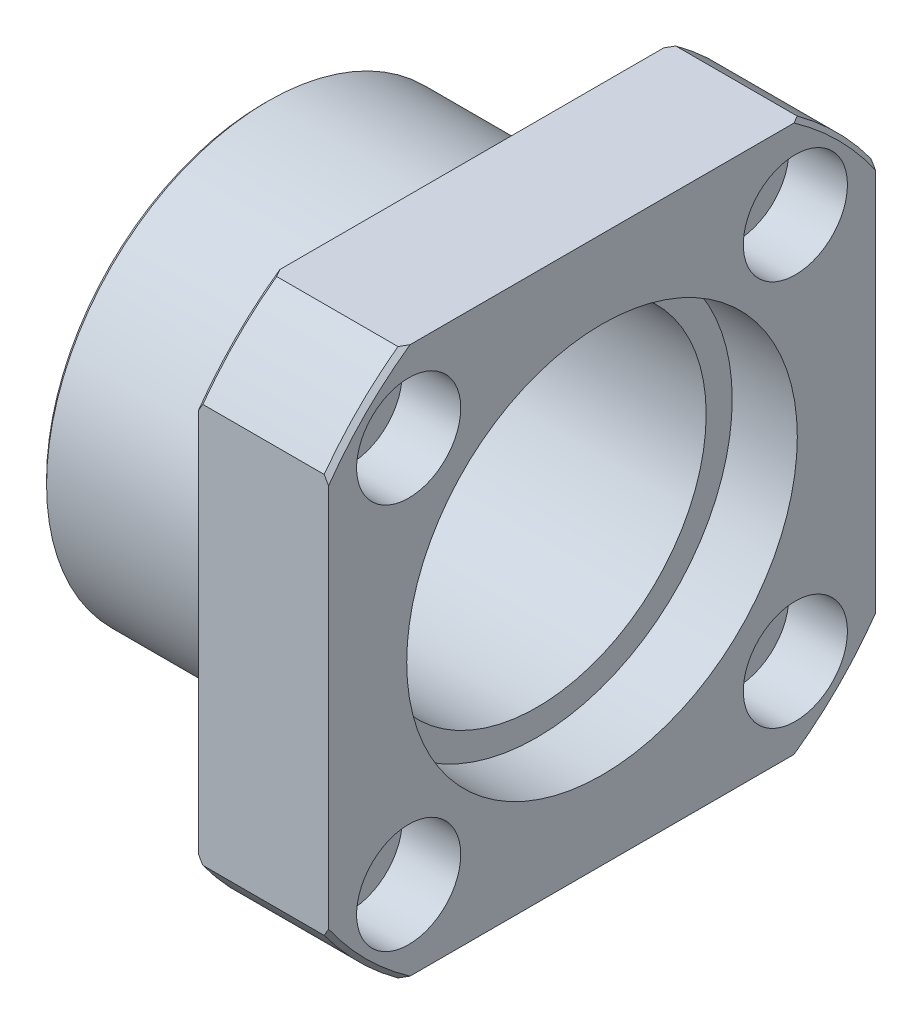
SolidWorks part; units mm, degrees
ref_plane "Front Plane" through (0, 0, 0) normal (0, 0, 1) x (1, 0, 0)
ref_plane "Top Plane" through (0, 0, 0) normal (0, 1, 0) x (1, 0, 0)
ref_plane "Right Plane" through (0, 0, 0) normal (1, 0, 0) x (0, 0, -1)
ref_plane "Plane1" through (26, 0, 0) normal (1, 0, 0) x (0, 0, -1)
sketch "Sketch1" plane through (26, 0, 0) normal (1, 0, 0) x (0, 0, -1)
  line L0 (21, -15.3297) -> (21, 15.3297)
  line L1 (15.3297, 21) -> (-15.3297, 21)
  line L2 (-21, 15.3297) -> (-21, -15.3297)
  line L3 (-15.3297, -21) -> (15.3297, -21)
  arc A0 (21, 15.3297) -> (15.3297, 21) centre (0, 0) ccw
  arc A1 (-15.3297, 21) -> (-21, 15.3297) centre (0, 0) ccw
  arc A2 (-21, -15.3297) -> (-15.3297, -21) centre (0, 0) ccw
  arc A3 (15.3297, -21) -> (21, -15.3297) centre (0, 0) ccw
extrude "Boss-Extrude1" add sketch "Sketch1" against normal blind 10
sketch "Sketch2" plane through (0, 0, 0) normal (0, 0, 1) x (1, 0, 0)
  line L0 (0, 17) -> (0, 0)
  line L1 (0, 0) -> (16, 0)
  line L2 (16, 0) -> (16, 17)
  line L3 (16, 17) -> (0, 17)
  line L4 (0, 0) -> (16, 0) construction
revolve "Revolve1" add sketch "Sketch2" angle 360 about L4 reverse direction yes
sketch "Sketch3" plane through (0, 0, 0) normal (0, 0, 1) x (1, 0, 0)
  line L0 (0, 7.25) -> (0, 0)
  line L1 (0, 0) -> (26, 0)
  line L2 (26, 0) -> (26, 15)
  line L3 (26, 15) -> (21, 15)
  line L4 (21, 15) -> (21, 13)
  line L5 (21, 13) -> (5, 13)
  line L6 (5, 13) -> (5, 7.25)
  line L7 (5, 7.25) -> (0, 7.25)
  line L8 (0, 0) -> (26, 0) construction
revolve "Cut-Revolve1" cut sketch "Sketch3" angle 360 about L8 reverse direction yes
hole_wizard "CBORE for M4 Hex Head Machine Screw1" positions "Sketch5" profile "Sketch4" counterbore size "M4" standard "ANSI Metric"
sketch "Sketch5" plane through (26, 0, 0) normal (1, 0, 0) x (0, 0, -1)
  point P0 (-14.8492, 14.8492)
  point P1 (14.8492, -14.8492)
  point P2 (14.8492, 14.8492)
  point P3 (-14.8492, -14.8492)
sketch "Sketch4" plane through (26, 14.8492, 14.8492) normal (0, 1, 0) x (0, 0, -1)
  line L0 (0, 0) -> (0, 26)
  line L1 (0, 26) -> (2.25, 26)
  line L3 (2.25, 26) -> (2.25, 4.5)
  line L4 (2.25, 4.5) -> (4, 4.5)
  line L5 (4, 4.5) -> (4, 0)
  line L7 (4, 0) -> (0, 0)
  line L11 (0, -6.35) -> (0, 107.95) construction
  dimension "Thru Hole Dia." = 4.5
  dimension "Thru Hole Depth" = 26
  dimension "C'Bore Dia." = 8
  dimension "C'Bore Depth" = 4.5
chamfer "Chamfer1" distance 0.34 angle 45 9 edges at (16, -18.3848, -18.3848) (16, 18.3848, 18.3848) (26, 18.3848, -18.3848) (16, -18.3848, 18.3848) (26, -18.3848, 18.3848) (0, 0, -17) (26, 18.3848, 18.3848) (26, -18.3848, -18.3848) (16, 18.3848, -18.3848)
fillet "Fillet1" radius 0.3 1 edges at (16, 0, -17) tangent propagation no
